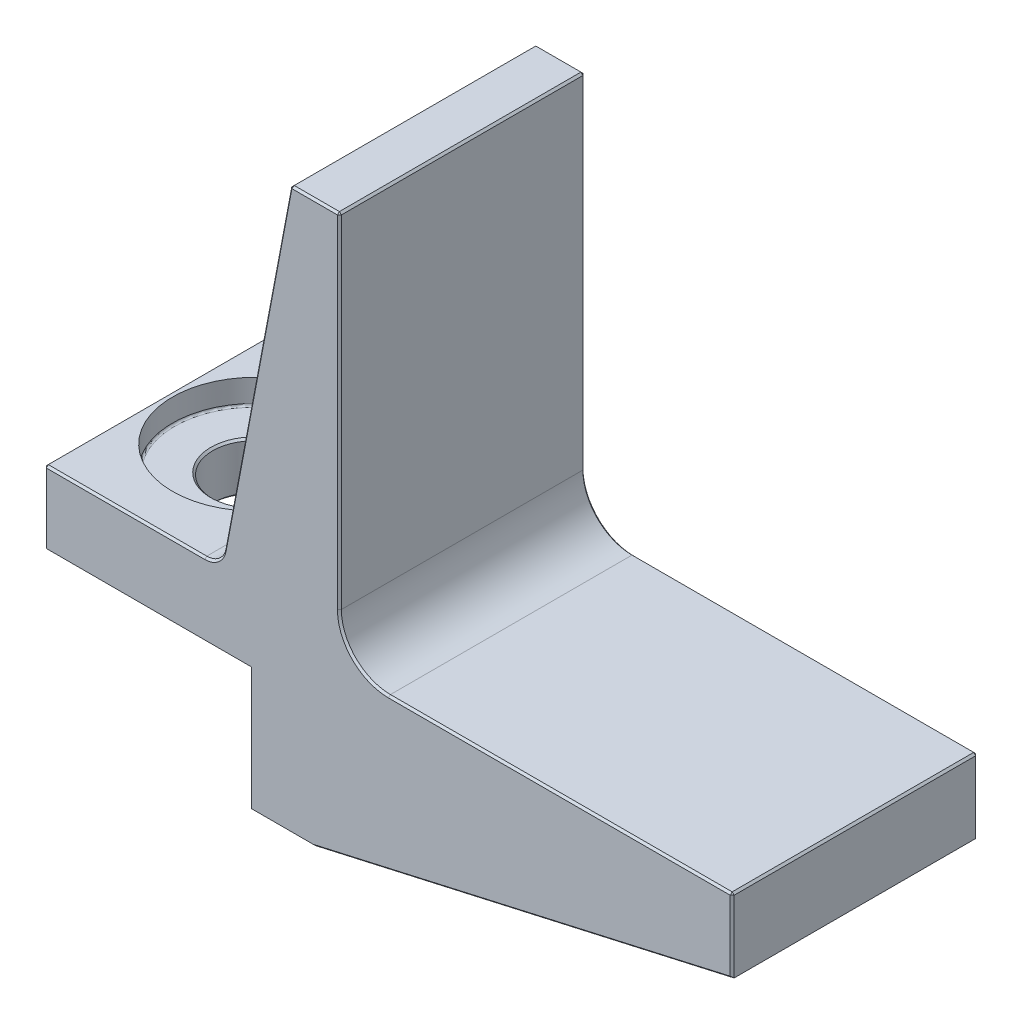
SolidWorks part; units mm, degrees
other "Markup1"
sketch "Sketch7" plane through (-38.1608, 50.8, 31.75) normal (-0.1424, 0.1459, 0.979) x (0.9898, 0.0098, 0.1425)
material "7075-T6 (SN)"
ref_plane "Front Plane" through (0, 0, 0) normal (0, 0, 1) x (1, 0, 0)
ref_plane "Top Plane" through (0, 0, 0) normal (0, 1, 0) x (1, 0, 0)
ref_plane "Right Plane" through (0, 0, 0) normal (1, 0, 0) x (0, 0, -1)
sketch "Sketch1" plane through (0, 0, 0) normal (0, 0, 1) x (1, 0, 0)
  line L0 (0, 0) -> (50.8, 0)
  line L1 (50.8, 0) -> (50.8, -9.525)
  line L2 (-11.6178, -5.8961) -> (-38.1608, -5.8961)
  line L3 (-38.1608, -5.8961) -> (-38.1608, 3.6289)
  line L4 (-38.1608, 3.6289) -> (-15.3008, 3.6289)
  line L5 (-15.3008, 3.6289) -> (-6.35, 50.8)
  line L6 (-6.35, 50.8) -> (0, 50.8)
  line L7 (0, 50.8) -> (0, 0)
  line L8 (-11.6178, -5.8961) -> (-11.6178, -21.7711)
  line L9 (-11.6178, -21.7711) -> (-3.3628, -21.7711)
  line L10 (-3.3628, -21.7711) -> (50.8, -9.525)
  dimension "D1" = 50.8
  dimension "D2" = 50.8
  dimension "D3" = 9.525
  dimension "D4" = 38.1608
  dimension "D5" = 6.35
  dimension "D6" = 22.86
  dimension "D7" = 26.543
  dimension "D8" = 9.525
  dimension "D9" = 15.875
  dimension "D10" = 8.255
  dimension "D11" = 3.6289
extrude "Boss-Extrude1" add sketch "Sketch1" along normal blind 31.75
hole_wizard "CBORE for 3/8 Binding Head Machine Screw1" positions "Sketch6" profile "Sketch3" counterbore size "3/8" standard "ANSI Inch" end condition through all
sketch "Sketch6" plane through (0, 3.6289, 0) normal (0, 1, 0) x (1, 0, 0)
  line L1 (-38.1608, -31.75) -> (-38.1608, 0) construction
  point P0 (-26.8578, -15.875)
  point P8 (-38.1608, -15.875)
  dimension "D1" = 11.303
sketch "Sketch3" plane through (-26.8578, 3.6289, 15.875) normal (1, 0, 0) x (0, 0, 1)
  line L0 (0, 0) -> (0, 25.4)
  line L1 (0, 25.4) -> (5.3975, 25.4)
  line L3 (5.3975, 25.4) -> (5.3975, 3.175)
  line L4 (10.5918, 3.175) -> (5.3975, 3.175)
  line L5 (10.5918, 3.175) -> (10.5918, 0)
  line L7 (10.5918, 0) -> (0, 0)
  line L11 (0, 0) -> (0, 107.95) construction
  dimension "Thru Hole Dia." = 10.795
  dimension "Thru Hole Depth" = 25.4
  dimension "C'Bore Depth" = 3.175
fillet "Fillet1" radius 2.54 1 edges at (-15.3008, 3.6289, 15.875)
fillet "Fillet2" radius 6.35 1 edges at (0, 0, 15.875)
chamfer "Chamfer1" distance 0.254 angle 45 31 edges at (-6.35, 50.8, 15.875) (-3.175, 50.8, 0) (-10.6293, 28.2477, 0) (-15.7842, 4.2126, 0) (-27.7825, 3.6289, 0) (-38.1608, -1.1336, 0) (-24.8893, -5.8961, 0) (50.8, -4.7625, 0) (28.575, 0, 0) (1.8599, 1.8599, 0) (0, 28.575, 0) (50.8, -4.7625, 31.75) (-24.8893, -5.8961, 31.75) (-38.1608, -5.8961, 15.875) (-38.1608, -1.1336, 31.75) (-38.1608, 3.6289, 15.875) (-27.7825, 3.6289, 31.75) (-15.7842, 4.2126, 31.75) (-10.6293, 28.2477, 31.75) (-3.175, 50.8, 31.75) (0, 50.8, 15.875) (0, 28.575, 31.75) (1.8599, 1.8599, 31.75) (28.575, 0, 31.75) (50.8, 0, 15.875) (-11.6178, -13.8336, 0) (-7.4903, -21.7711, 0) (23.7186, -15.6481, 0) (23.7186, -15.6481, 31.75) (-7.4903, -21.7711, 31.75) (-11.6178, -13.8336, 31.75) first distance on face at (-3.175, 50.8, 15.875) first distance on face at (-12.0626, 20.6941, 15.5915) first distance on face at (-15.9703, 4.4374, 5.5493) first distance on face at (-27.664, 3.6289, 15.875) first distance on face at (-38.1608, -1.1336, 15.875) first distance on face at (-32.2553, -5.8961, 15.875) first distance on face at (50.8, -4.7625, 15.875) first distance on face at (-2.6597, 4.1753, 0) first distance on face at (2.5174, 2.5174, 15.875) first distance on face at (0, 28.575, 15.875) first distance on face at (-15.9703, 4.4374, 26.2007) first distance on face at (-2.6597, 4.1753, 31.75) first distance on face at (-11.6178, -13.8336, 15.875) first distance on face at (-7.4903, -21.7711, 15.875) first distance on face at (23.7186, -15.6481, 15.875)
fillet "Fillet3" radius 0.254 1 edges at (-26.8578, 0.4539, 26.4668)
chamfer "Chamfer2" distance 0.254 angle 45 1 edges at (-32.2553, -5.8961, 15.875)
chamfer "Chamfer3" distance 0.254 angle 45 1 edges at (-26.8578, 0.4539, 21.2725)
